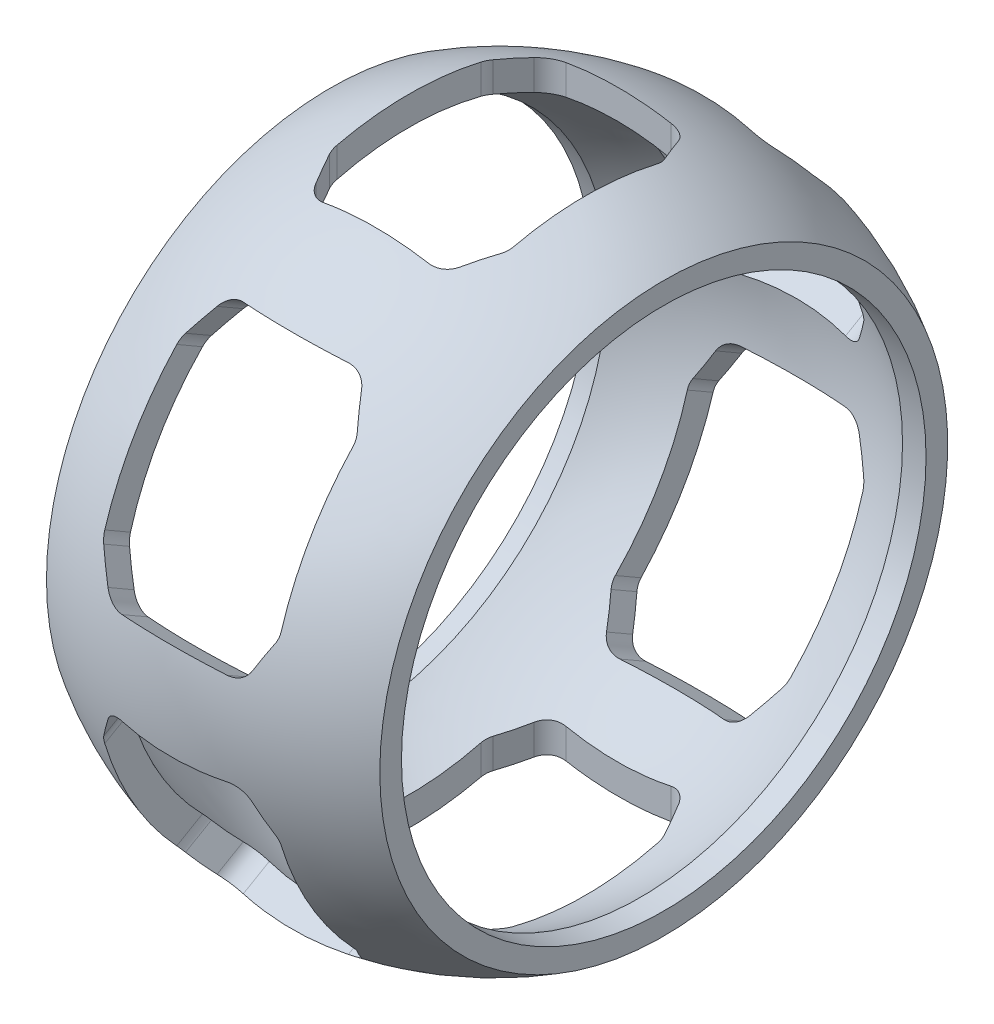
SolidWorks part; units mm, degrees
ref_plane "Front Plane" through (0, 0, 0) normal (0, 0, 1) x (1, 0, 0)
ref_plane "Top Plane" through (0, 0, 0) normal (0, 1, 0) x (1, 0, 0)
ref_plane "Right Plane" through (0, 0, 0) normal (1, 0, 0) x (0, 0, -1)
sketch "Sketch2" plane through (0, 0, 0) normal (0, 1, 0) x (1, 0, 0)
  line L0 (0, 0) -> (129.0301, 0) construction
  line L1 (0, 0) -> (162, 0) construction
  line L2 (0, 25.7597) -> (0, 23.6145)
  line L3 (0, 23.6145) -> (1.5616, 23.6145)
  line L5 (30.2387, 25.7597) -> (30.2387, 23.7937)
  line L6 (30.2387, 23.7937) -> (28.1056, 23.7937)
  arc A0 (0, 25.7597) -> (30.2387, 25.7597) centre (15.1194, 0.5514) cw
  arc A1 (1.5616, 23.6145) -> (28.1056, 23.7937) centre (14.9786, 2.2257) cw
  dimension "D1" = 162
revolve "Revolve1" add sketch "Sketch2" angle 360 about L0
sketch "Sketch3" plane through (0, 0, 0) normal (0, 1, 0) x (1, 0, 0)
  line L0 (0, 0) -> (30.2387, 0) construction
  line L1 (30.2387, -25.7597) -> (30.2387, 25.7597) construction
  line L2 (7.3305, 7.4223) -> (8.5666, 9.8944)
  line L3 (10.3554, -11) -> (19.8833, -11)
  line L4 (7.1194, -6.5279) -> (7.1194, 6.5279)
  line L5 (10.3554, 11) -> (19.8833, 11)
  line L6 (23.1194, -6.5279) -> (23.1194, 6.5279)
  line L7 (7.1194, -11) -> (23.1194, 11) construction
  line L8 (7.1194, 11) -> (23.1194, -11) construction
  line L9 (21.6721, -9.8944) -> (22.9082, -7.4223)
  line L10 (21.6721, 9.8944) -> (22.9082, 7.4223)
  line L11 (7.3305, -7.4223) -> (8.5666, -9.8944)
  arc A0 (21.6721, -9.8944) -> (19.8833, -11) centre (19.8833, -9) cw
  arc A1 (22.9082, -7.4223) -> (23.1194, -6.5279) centre (21.1194, -6.5279) ccw
  arc A2 (22.9082, 7.4223) -> (23.1194, 6.5279) centre (21.1194, 6.5279) cw
  arc A3 (21.6721, 9.8944) -> (19.8833, 11) centre (19.8833, 9) ccw
  arc A4 (8.5666, 9.8944) -> (10.3554, 11) centre (10.3554, 9) cw
  arc A5 (7.3305, 7.4223) -> (7.1194, 6.5279) centre (9.1194, 6.5279) ccw
  arc A6 (8.5666, -9.8944) -> (10.3554, -11) centre (10.3554, -9) ccw
  arc A7 (7.3305, -7.4223) -> (7.1194, -6.5279) centre (9.1194, -6.5279) cw
  point P3 (15.1194, 0)
  point P6 (15.1194, 0)
  point P21 (21.1194, -11)
  point P24 (23.1194, -7)
  point P27 (23.1194, 7)
  point P30 (21.1194, 11)
  point P33 (9.1194, 11)
  point P36 (7.1194, 7)
  point P39 (9.1194, -11)
  point P42 (7.1194, -7)
  dimension "D1" = 22
  dimension "D11" = 2
  dimension "D2" = 16
  dimension "D3" = 4
  dimension "D4" = 2
  dimension "D5" = 2
  dimension "D6" = 4
  dimension "D7" = 2
  dimension "D8" = 4
  dimension "D9" = 2
  dimension "D10" = 4
extrude "Cut-Extrude1" cut sketch "Sketch3" against normal through all both and the other way through all
pattern_circular "CirPattern1" count 3 over 360 about axis through (30.2387, 0, 0) along (-1, 0, 0) of "Cut-Extrude1"
ref_plane "Plane1" through (15.1194, 0, 0) normal (-1, 0, 0) x (0, 0, 1)
sketch "Sketch4" plane through (15.1194, 0, 0) normal (-1, 0, 0) x (0, 0, 1)
  line L0 (0, -38.8939) -> (0, 38.8939)
  line L1 (48.9648, 28.2699) -> (-48.9648, -28.2699)
  line L2 (48.2057, -27.8316) -> (-48.2057, 27.8316)
  point P6 (0, 0)
  point P7 (27.5889, 16.1852)
  point P8 (0, 0)
  point P10 (-24.9732, 14.4183)
  point P12 (0, 0)
  dimension "D1" = 60
  dimension "D2" = 60
sketch "Sketch5" plane through (0, 0, 11) normal (0, 0, -1) x (-1, 0, 0)
  spline S0 degree 3 poles (186.661, 1958.9502) (148.3451, 399.8302) (73.5174, -27.8201) (-15.9038, -27.853) (-16.6995, -27.8187) (-57.076, -24.2951) (-108.2681, 68.2176) (1978.6222, -16.1249) knots -27.385822 -27.385822 -27.385822 -27.385822 0.5 0.5 0.75 0.75 13.168274 13.168274 13.168274 13.168274 only from (-10.3554, -27.4345) to (-19.8833, -27.4345) construction
  spline S1 degree 3 poles (-10.3554, -27.4345) (-11.9355, -27.7141) (-13.5202, -27.8521) (-15.9038, -27.853) (-16.6995, -27.8187) (-18.2931, -27.6797) (-19.0946, -27.574) (-19.8833, -27.4345) knots 0 0 0 0 0.5 0.5 0.75 0.75 1 1 1 1
sketch "Sketch6" plane through (0, 0, -11) normal (0, 0, 1) x (1, 0, 0)
  spline S0 degree 3 poles (216.8997, 1958.9502) (178.5838, 399.8302) (103.7561, -27.8201) (14.3349, -27.853) (13.5392, -27.8187) (-26.8373, -24.2951) (-78.0293, 68.2176) (2008.8609, -16.1249) knots -27.385822 -27.385822 -27.385822 -27.385822 0.5 0.5 0.75 0.75 13.168274 13.168274 13.168274 13.168274 only from (19.8833, -27.4345) to (10.3554, -27.4345) construction
  spline S1 degree 3 poles (19.8833, -27.4345) (18.3032, -27.7141) (16.7185, -27.8521) (14.3349, -27.853) (13.5392, -27.8187) (11.9456, -27.6797) (11.1441, -27.574) (10.3554, -27.4345) knots 0 0 0 0 0.5 0.5 0.75 0.75 1 1 1 1
ref_axis "Axis1" through (35.181, 0, 0) along (-1, 0, 0)
ref_plane "Plane2" through (0, 0, 0) normal (0, 0.866, -0.5) x (0, -0.5, -0.866)
sketch "Sketch7" plane through (0, 0, 0) normal (0, 0.866, -0.5) x (0, -0.5, -0.866)
  circle A0 centre (0, -15.1194) radius 33.6796
